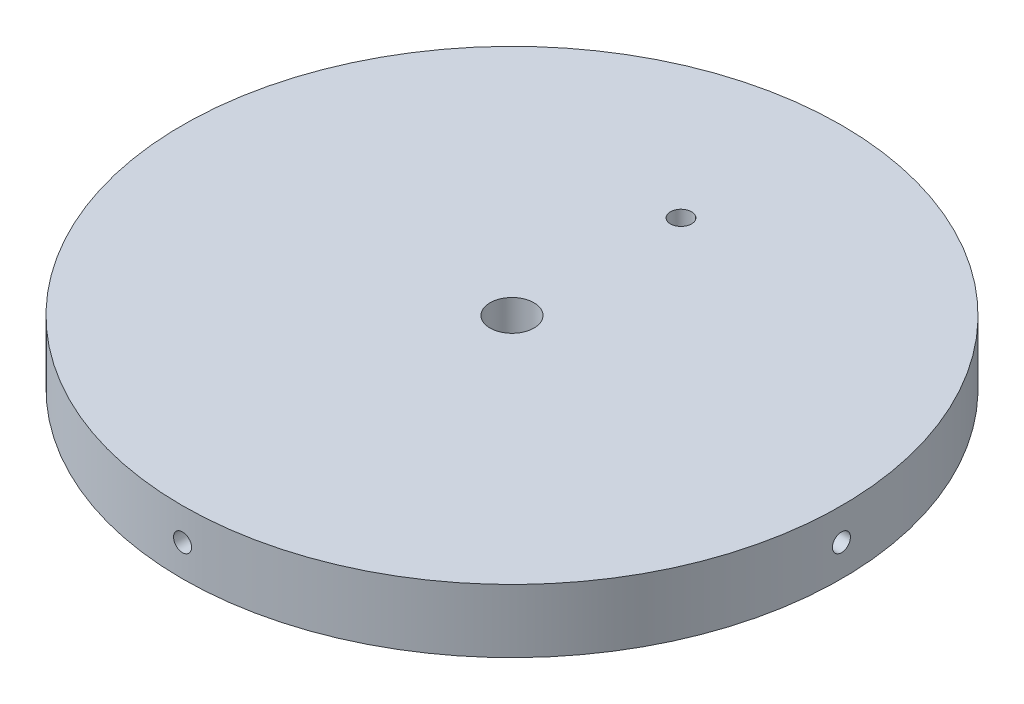
SolidWorks part; units mm, degrees
ref_plane "Front Plane" through (0, 0, 0) normal (0, 0, 1) x (1, 0, 0)
ref_plane "Top Plane" through (0, 0, 0) normal (0, 1, 0) x (1, 0, 0)
ref_plane "Right Plane" through (0, 0, 0) normal (1, 0, 0) x (0, 0, -1)
sketch "Sketch1" plane through (0, 0, 0) normal (0, 1, 0) x (1, 0, 0)
  circle A0 centre (0, 0) radius 49.53
  circle A1 centre (0, 0) radius 3.3
  circle A2 centre (0, 25.4) radius 1.5875
  dimension "D1" = 99.06
  dimension "D2" = 6.6
  dimension "D3" = 3.175
  dimension "D4" = 25.4
extrude "Boss-Extrude1" add sketch "Sketch1" along normal mid plane 9.525
ref_plane "Plane1" through (0, 0, 50.8) normal (0, 0, 1) x (1, 0, 0)
sketch "Sketch2" plane through (0, 0, 50.8) normal (0, 0, 1) x (1, 0, 0)
  circle A0 centre (0, 0) radius 1.3526
  dimension "D1" = 2.7051
extrude "Cut-Extrude1" cut sketch "Sketch2" against normal blind 12.7
sketch "Sketch3" plane through (0, 0, 0) normal (0, 0, 1) x (1, 0, 0)
  line L0 (0, 4.7625) -> (0, -4.7625)
  line L1 (49.53, 4.7625) -> (-49.53, 4.7625) construction
  line L2 (-49.53, -4.7625) -> (49.53, -4.7625) construction
pattern_circular "CirPattern1" count 4 over 360 about axis through (0, 4.7625, 0) along (0, -1, 0) of "Cut-Extrude1"
equation "\"Body_Tube_OD\"= 4.024in"
equation "\"Body_Tube_ID\"= 3.90in"
equation "\"D1@Sketch1\"=\"Body_Tube_ID\""
